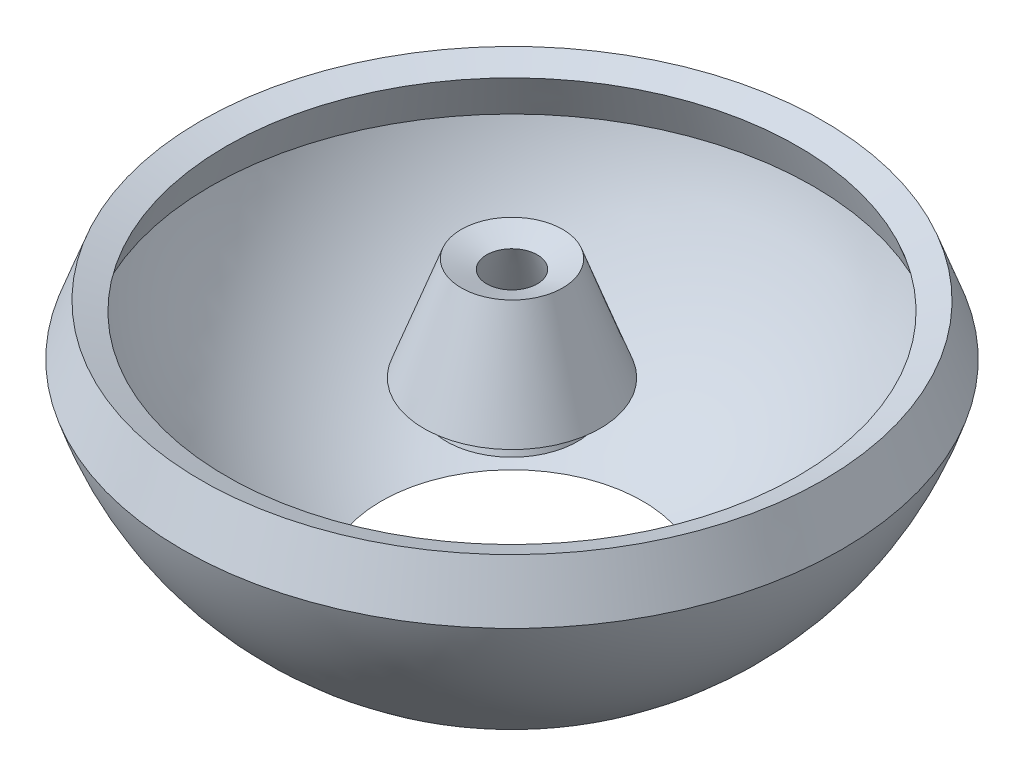
SolidWorks part; units mm, degrees
ref_plane "Front Plane" through (0, 0, 0) normal (0, 0, 1) x (1, 0, 0)
ref_plane "Top Plane" through (0, 0, 0) normal (0, 1, 0) x (1, 0, 0)
ref_plane "Right Plane" through (0, 0, 0) normal (1, 0, 0) x (0, 0, -1)
sketch "Sketch2" plane through (0, 0, 0) normal (0, 0, 1) x (1, 0, 0)
  line L0 (0, 0) -> (0, -31.75) construction
  line L1 (0, 0) -> (0, -77) construction
  line L2 (-15.75, -52) -> (15.75, -52) construction
  line L3 (-15.75, -52) -> (-15.75, -11.5) construction
  line L4 (-15.75, -11.5) -> (15.75, -11.5) construction
  line L5 (15.75, -52) -> (15.75, -11.5) construction
  line L6 (-15.75, -52) -> (15.75, -11.5) construction
  line L7 (-15.75, -11.5) -> (15.75, -52) construction
  line L8 (-5, -77) -> (5, -77) construction
  line L9 (-5, -77) -> (-5, -52) construction
  line L10 (-5, -52) -> (5, -52) construction
  line L11 (5, -77) -> (5, -52) construction
  line L12 (-5, -77) -> (5, -52) construction
  line L13 (-5, -52) -> (5, -77) construction
  line L14 (26.3356, -72.3563) -> (0, 0) construction
  line L15 (-101.6, -57) -> (101.6, -57) construction
  line L16 (-101.6, -57) -> (-101.6, -77) construction
  line L17 (-101.6, -77) -> (101.6, -77) construction
  line L18 (101.6, -57) -> (101.6, -77) construction
  line L19 (-101.6, -57) -> (101.6, -77) construction
  line L20 (-101.6, -77) -> (101.6, -57) construction
  line L21 (2.9849, -54.2508) -> (-10.8669, -16.1933) construction
  line L22 (2.9849, -54.2508) -> (32.5852, -43.4772) construction
  line L23 (-10.8669, -16.1933) -> (18.7334, -5.4196) construction
  line L25 (2.9849, -54.2508) -> (18.7334, -5.4196) construction
  line L26 (-10.8669, -16.1933) -> (32.5852, -43.4772) construction
  line L27 (18.7334, -5.4196) -> (32.5852, -43.4772) construction
  line L28 (21.6371, -74.0664) -> (13.0866, -50.5741) construction
  line L29 (21.6371, -74.0664) -> (31.034, -70.6462) construction
  line L30 (13.0866, -50.5741) -> (22.4835, -47.1539) construction
  line L31 (31.034, -70.6462) -> (22.4835, -47.1539) construction
  line L32 (21.6371, -74.0664) -> (22.4835, -47.1539) construction
  line L33 (13.0866, -50.5741) -> (31.034, -70.6462) construction
  line L34 (-75.9776, -88.3117) -> (-69.1372, -107.1056) construction
  line L35 (-75.9776, -88.3117) -> (114.9679, -18.8132) construction
  line L36 (-69.1372, -107.1056) -> (121.8083, -37.6071) construction
  line L37 (114.9679, -18.8132) -> (121.8083, -37.6071) construction
  line L38 (-75.9776, -88.3117) -> (121.8083, -37.6071) construction
  line L39 (-69.1372, -107.1056) -> (114.9679, -18.8132) construction
  line L40 (104.3421, 25) -> (163.3437, -137.1056)
  line L41 (106.1573, 31.708) -> (172.4045, -150.3046) construction
  line L42 (-50, -25) -> (50, -25) construction
  line L43 (-50, -25) -> (-50, 25) construction
  line L44 (-50, 25) -> (50, 25) construction
  line L45 (50, -25) -> (50, 25) construction
  line L46 (-50, -25) -> (50, 25) construction
  line L47 (-50, 25) -> (50, -25) construction
  line L48 (50, 25) -> (104.3421, 25) construction
  line L49 (24.9744, -19.6429) -> (28.3946, -29.0398)
  line L50 (20.1322, -48.0097) -> (74.6794, -28.1562) construction
  line L51 (26.6845, -24.3413) -> (111.1159, 6.3892)
  line L52 (0, 0) -> (0, -127.9692) construction
  line L53 (121.8083, -37.6071) -> (114.9679, -18.8132)
  line L54 (114.9679, -18.8132) -> (24.1936, -51.8524) construction
  line L55 (24.1936, -51.8524) -> (22.4835, -47.1539)
  line L56 (22.4835, -47.1539) -> (32.5852, -43.4772)
  line L57 (32.5852, -43.4772) -> (18.7334, -5.4196)
  line L58 (18.7334, -5.4196) -> (0, -12.238) construction
  line L59 (0, -12.238) -> (0, -127.4816) construction
  circle A0 centre (0, 0) radius 10 construction
  arc A1 (0, -77) -> (26.3356, -72.3563) centre (0, 0) ccw construction
  arc A2 (101.6, -77) -> (121.8083, -37.6071) centre (0, 0) ccw
  arc A3 (101.6, -77) -> (0, -127.4816) centre (0, 0) cw
  point P8 (0, -64.5)
  point P13 (0, -67)
  point P21 (10.8591, -29.8352)
  point P22 (22.0603, -60.6102)
  point P23 (22.9153, -62.9594)
  dimension "D1" = 20
  dimension "D11" = 20
  dimension "D2" = 31.5
  dimension "D3" = 40.5
  dimension "D4" = 11.5
  dimension "D5" = 25
  dimension "D6" = 10
  dimension "D7" = 0
  dimension "D8" = 20
  dimension "D9" = 10
  dimension "D10" = 203.2
  dimension "D12" = 31.5
  dimension "D13" = 0
  dimension "D14" = 40.5
  dimension "D15" = 15.75
  dimension "D16" = 11.5
  dimension "D17" = 25
  dimension "D18" = 10
  dimension "D19" = 5
  dimension "D20" = 203.2
  dimension "D21" = 0
  dimension "D22" = 20
  dimension "D23" = 0
  dimension "D24" = 5
  dimension "D25" = 30
  dimension "D26" = 5
  dimension "D27" = 100
  dimension "D28" = 50
  dimension "D29" = 10
  dimension "D30" = 1
  dimension "D31" = 15
  dimension "D32" = 4
sketch "Sketch3" plane through (0, 0, 0) normal (0, 0, 1) x (1, 0, 0)
  line L0 (24.2904, -17.7635) -> (29.0786, -30.9192)
  line L3 (24.9744, -19.6429) -> (28.3946, -29.0398) construction
  line L4 (29.0786, -30.9192) -> (24.2904, -17.7635)
  line L5 (29.0786, -30.9192) -> (31.8977, -29.8931)
  line L6 (24.2904, -17.7635) -> (27.1094, -16.7374)
  line L7 (31.8977, -29.8931) -> (27.1094, -16.7374)
  point P5 (26.6845, -24.3413)
  dimension "D1" = 0
  dimension "D2" = 0
  dimension "D3" = 14
  dimension "D4" = 3
revolve "Revolve-Thin2" add sketch "Sketch2" angle 360 about L52 wall 10
revolve "Revolve-Thin6" add sketch "Sketch2<8>" angle 360 about L0 wall 10
sketch "Sketch2<8>" plane through (0, 0, 0) normal (0, 0, 1) x (1, 0, 0) same geometry as "Sketch2"
revolve "Revolve-Thin7" add sketch "Sketch2<10>" angle 360 about L0 wall 10
sketch "Sketch2<10>" plane through (0, 0, 0) normal (0, 0, 1) x (1, 0, 0) same geometry as "Sketch2"
sketch "Sketch5" plane through (0, 0, 0) normal (0, 0, 1) x (1, 0, 0)
  line L1 (-69.1372, -107.1056) -> (106.8474, -107.1056)
  line L2 (-69.1372, -107.1056) -> (-69.1372, -152.5172)
  line L3 (-69.1372, -152.5172) -> (106.8474, -152.5172)
  line L4 (106.8474, -107.1056) -> (106.8474, -152.5172)
extrude "Cut-Extrude1" cut sketch "Sketch5" against normal through all both and the other way through all
